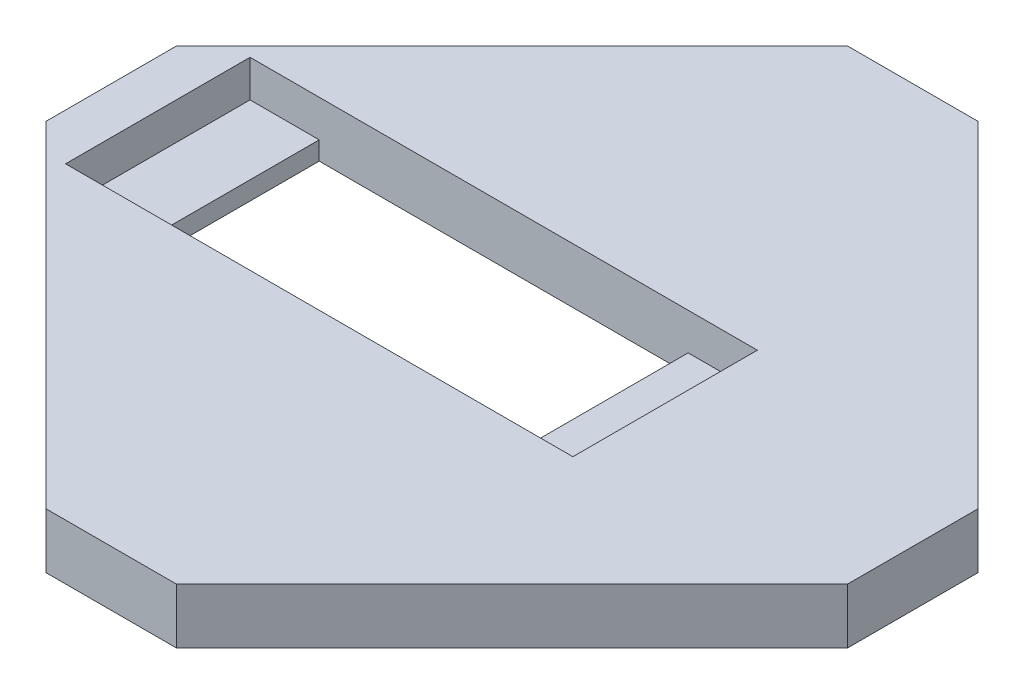
SolidWorks part; units mm, degrees
ref_plane "Front Plane" through (0, 0, 0) normal (0, 0, 1) x (1, 0, 0)
ref_plane "Top Plane" through (0, 0, 0) normal (0, 1, 0) x (1, 0, 0)
ref_plane "Right Plane" through (0, 0, 0) normal (1, 0, 0) x (0, 0, -1)
sketch "Sketch1" plane through (0, 0, 0) normal (0, 1, 0) x (1, 0, 0)
  line L0 (7.0711, 43.4503) -> (43.4503, 7.0711)
  line L21 (-38.4, -10) -> (16.6, -10)
  line L22 (-38.4, -10) -> (-38.4, 10)
  line L23 (-38.4, 10) -> (16.6, 10)
  line L24 (16.6, -10) -> (16.6, 10)
  line L25 (-38.4, -10) -> (16.6, 10) construction
  line L26 (-38.4, 10) -> (16.6, -10) construction
  line L27 (-30.9, 10) -> (9.1, 10)
  line L28 (-30.9, 10) -> (-30.9, -10)
  line L29 (-30.9, -10) -> (9.1, -10)
  line L30 (9.1, 10) -> (9.1, -10)
  line L31 (-30.9, 10) -> (9.1, -10) construction
  line L32 (-30.9, -10) -> (9.1, 10) construction
  line L33 (43.4503, -7.0711) -> (7.0711, -43.4503)
  line L34 (-7.0711, -43.4503) -> (-43.4503, -7.0711)
  line L35 (-43.4503, 7.0711) -> (-7.0711, 43.4503)
  line L36 (-43.4503, -7.0711) -> (-43.4503, 7.0711)
  line L37 (-7.0711, 43.4503) -> (7.0711, 43.4503)
  line L38 (43.4503, 7.0711) -> (43.4503, -7.0711)
  line L39 (7.0711, -43.4503) -> (-7.0711, -43.4503)
  circle A1 centre (0, 0) radius 4.4413
  point P1 (-20.8239, -57.1063)
  point P2 (50.5213, 0)
  point P3 (-9.7385, 62.4844)
  point P4 (0, -50.5213)
  point P5 (-50.5213, 0)
  point P6 (0, 50.5213)
  point P7 (33.6249, -4.2877)
  point P8 (0, 0)
  point P9 (-57.1775, 0)
  point P10 (-5.663, -39.5001)
  point P12 (-10.9, 0)
  point P18 (-53.102, 0)
  point P19 (-10.9, 0)
  point P24 (30.8536, 0)
  point P33 (-43.4503, 0)
  point P34 (-30.9, 0)
  point P35 (0, 0)
  point P36 (-43.4309, -7.0711)
  point P37 (42.4472, -7.0711)
  point P38 (0, 0)
  point P39 (0, 43.4503)
  point P40 (7.0711, -43.4409)
  dimension "D1" = 55
  dimension "D2" = 20
  dimension "D3" = 40
  dimension "D4" = 16.6
  dimension "D5" = 1.5
extrude "Boss-Extrude1" add sketch "Sketch1" along normal blind 6 contours L34 L35 L24 L21 L22 L23 region at (24.3917, 0, -24.3917)
extrude "Boss-Extrude2" add sketch "Sketch1<3>" along normal blind 2 contours L28 L23 L22 L21 | L23 L30 L21 L24 region at (-34.65, 0, 0) region at (12.85, 0, 0)
sketch "Sketch1<3>" plane through (0, 0, 0) normal (0, 1, 0) x (1, 0, 0) same geometry as "Sketch1"
ref_plane "Plane2" through (0, 0, 0) normal (1, 0, 0) x (0, 0, -1)
ref_plane "Plane3" through (0, 0, 0) normal (0, 0, 1) x (1, 0, 0)
sketch "Sketch2" plane through (0, 0, 0) normal (0, 0, 1) x (1, 0, 0)
  line L38 (16.6272, 6) -> (16.6272, 6.8511)
  line L39 (43.4503, 6) -> (7.0711, 6) construction
  line L40 (16.6272, 6.8511) -> (24.6202, 6.8511)
  line L41 (24.6202, 6.8511) -> (53.3204, -23.493)
  line L42 (53.3204, -23.493) -> (45.3604, -23.493)
  line L43 (45.3604, -23.493) -> (23.9451, -0.8511)
  line L44 (23.9451, -0.8511) -> (16.6272, -0.8511)
  line L45 (16.6272, -0.8511) -> (16.6272, 0)
  line L46 (43.4503, 0) -> (7.0711, 0) construction
  line L47 (16.6272, 0) -> (43.4503, 0)
  line L48 (43.4503, 0) -> (43.4503, 6)
  line L49 (43.4503, 6) -> (16.6272, 6)
  line L50 (73.4888, -44.8167) -> (53.3204, -23.493) construction
  line L51 (53.3204, -23.493) -> (45.3585, -23.493) construction
  point P1 (21.0328, -2.2851)
  point P15 (27.2467, -1.8701)
  point P16 (18.8528, -0.9599)
  point P19 (22.4224, 6.8502)
  point P20 (38.8275, -18.9125)
  dimension "D1" = 7.96
extrude "Boss-Extrude3" [suppressed] add sketch "Sketch2" along normal mid plane 14.14 separate body
mirror "Mirror1" [suppressed] about plane through (0, 0, 0) normal (1, 0, 0) of bodies 103
ref_plane "Plane4" through (0, 0, 0) normal (-0.7071, 0, 0.7071) x (0.7071, 0, 0.7071)
mirror "Mirror3" [suppressed] about plane through (0, 0, 0) normal (-0.7071, 0, 0.7071) of bodies 103 104
